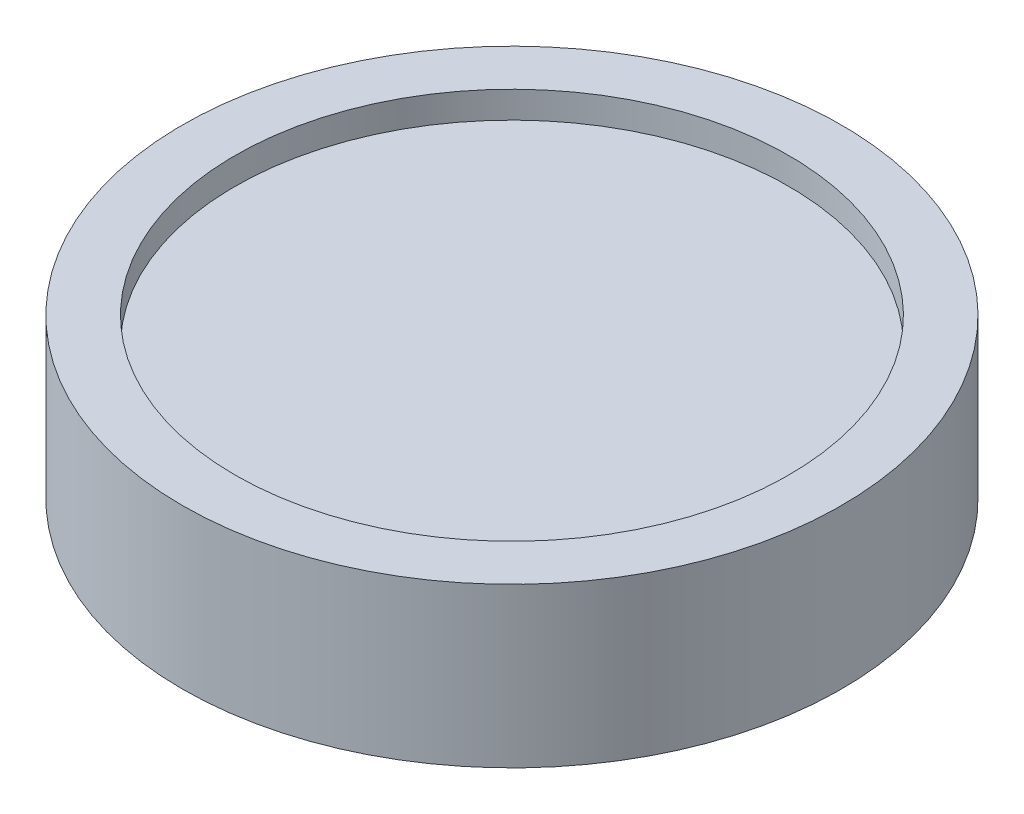
SolidWorks part; units mm, degrees
ref_plane "Front Plane" through (0, 0, 0) normal (0, 0, 1) x (1, 0, 0)
ref_plane "Top Plane" through (0, 0, 0) normal (0, 1, 0) x (1, 0, 0)
ref_plane "Right Plane" through (0, 0, 0) normal (1, 0, 0) x (0, 0, -1)
sketch "Sketch1" plane through (0, 0, 0) normal (0, 1, 0) x (1, 0, 0)
  circle A0 centre (0, 0) radius 10.5
  dimension "D1" = 21
extrude "Boss-Extrude1" add sketch "Sketch1" along normal blind 2
extrude "Boss-Extrude2" add sketch "Sketch1<2>" against normal blind 2
sketch "Sketch1<2>" plane through (0, 0, 0) normal (0, 1, 0) x (1, 0, 0) same geometry as "Sketch1"
sketch "Sketch2" plane through (0, 0, 0) normal (0, 1, 0) x (1, 0, 0)
  circle A0 centre (0, 0) radius 10.5 construction
  circle A1 centre (0, 0) radius 10.5
  circle A2 centre (0, 0) radius 12.5
  dimension "D1" = 25
extrude "Boss-Extrude3" add sketch "Sketch2" along normal blind 3.015 and the other way blind 3.015
